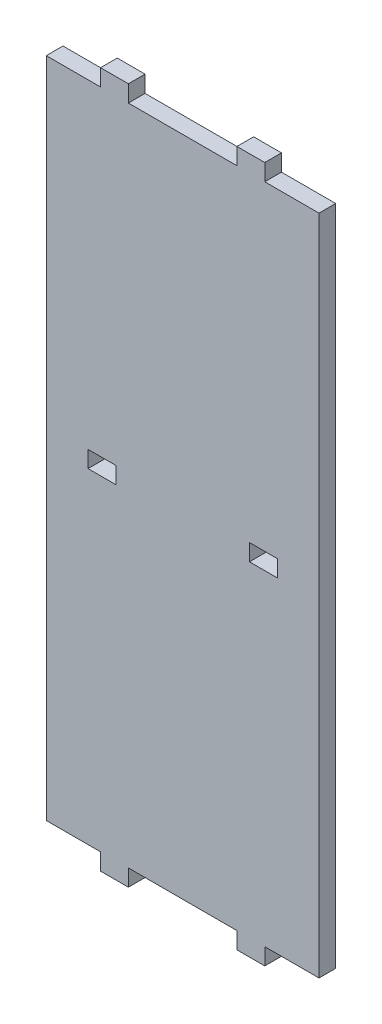
SolidWorks part; units mm, degrees
ref_plane "Plan de face" through (0, 0, 0) normal (0, 0, 1) x (1, 0, 0)
ref_plane "Plan de dessus" through (0, 0, 0) normal (0, 1, 0) x (1, 0, 0)
ref_plane "Plan de droite" through (0, 0, 0) normal (1, 0, 0) x (0, 0, -1)
sketch "Esquisse1" plane through (0, 0, 0) normal (0, 0, 1) x (1, 0, 0)
  line L0 (0, 176.8395) -> (0, -221.1538) construction
  line L1 (-49, 119) -> (49, 119)
  line L2 (-49, 119) -> (-49, -119)
  line L3 (-49, -119) -> (49, -119)
  line L4 (49, 119) -> (49, -119)
  line L5 (376.8436, 0) -> (-286.1998, 0) construction
  line L6 (-376.8436, 0) -> (286.1998, 0) construction
  line L7 (34, 4) -> (24, 4)
  line L8 (34, 4) -> (34, -2)
  line L9 (34, -2) -> (24, -2)
  line L10 (24, 4) -> (24, -2)
  line L11 (-24, 4) -> (-24, -2)
  line L12 (-34, -2) -> (-24, -2)
  line L13 (-34, 4) -> (-34, -2)
  line L14 (-34, 4) -> (-24, 4)
  dimension "D1" = 238
  dimension "D2" = 98
  dimension "D3" = 49
  dimension "D4" = 119
  dimension "D5" = 10
  dimension "D6" = 6
  dimension "D7" = 117
  dimension "D8" = 15
extrude "Boss.-Extru.1" add sketch "Esquisse1" along normal blind 6
sketch "Esquisse2" plane through (0, 0, 6) normal (0, 0, 1) x (1, 0, 0)
  line L1 (-49, -119) -> (49, -119) construction
  line L2 (29.5, -119) -> (19.5, -119)
  line L3 (29.5, -119) -> (29.5, -125)
  line L4 (29.5, -125) -> (19.5, -125)
  line L6 (154.6429, 0) -> (-167.6281, 0) construction
  line L7 (19.5, -119) -> (19.5, -125)
  line L8 (-49, 119) -> (-49, -119) construction
  line L9 (-19.5, -119) -> (-29.5, -119)
  line L10 (-19.5, -119) -> (-19.5, -125)
  line L11 (-19.5, -125) -> (-29.5, -125)
  line L12 (-29.5, -119) -> (-29.5, -125)
  line L13 (-29.5, 119) -> (-29.5, 125)
  line L14 (-19.5, 125) -> (-29.5, 125)
  line L15 (-19.5, 119) -> (-19.5, 125)
  line L16 (-19.5, 119) -> (-29.5, 119)
  line L17 (19.5, 119) -> (19.5, 125)
  line L18 (29.5, 125) -> (19.5, 125)
  line L19 (29.5, 119) -> (29.5, 125)
  line L20 (29.5, 119) -> (19.5, 119)
  dimension "D1" = 6
  dimension "D2" = 6
  dimension "D3" = 10
  dimension "D4" = 10
  dimension "D5" = 19.5
  dimension "D6" = 39
extrude "Boss.-Extru.2" add sketch "Esquisse2" against normal blind 6
equation "\"D3@Esquisse1\"=\"D2@Esquisse1\"/2"
equation "\"D4@Esquisse1\"=\"D1@Esquisse1\"/2"
